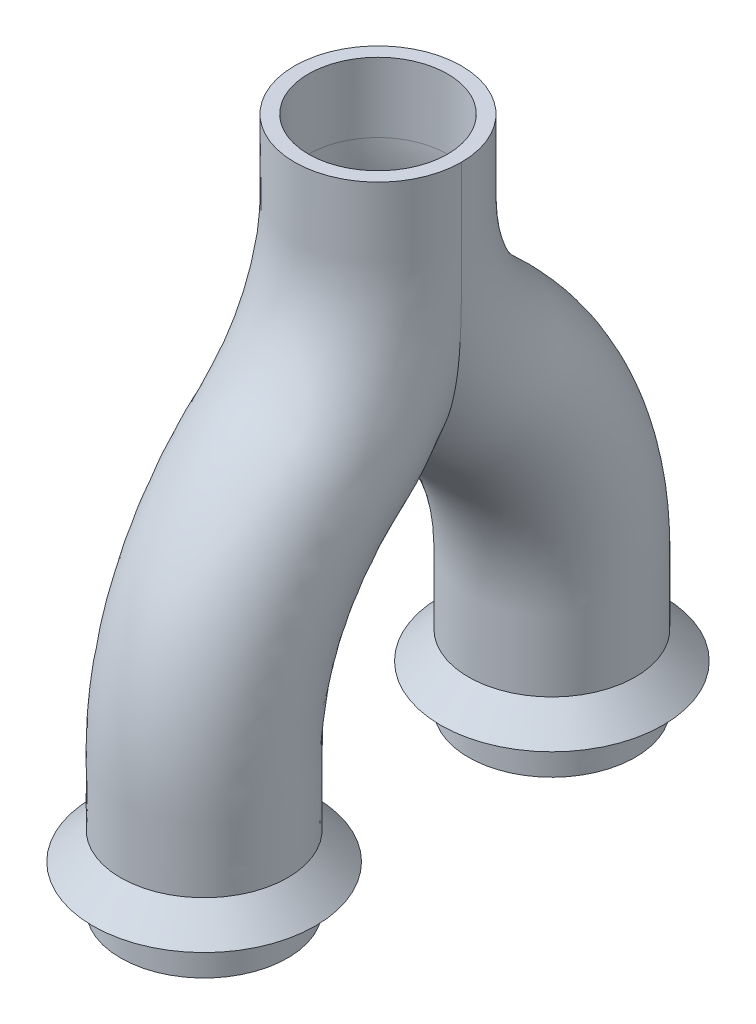
SolidWorks part; units mm, degrees
ref_plane "Front Plane" through (0, 0, 0) normal (0, 0, 1) x (1, 0, 0)
ref_plane "Top Plane" through (0, 0, 0) normal (0, 1, 0) x (1, 0, 0)
ref_plane "Right Plane" through (0, 0, 0) normal (1, 0, 0) x (0, 0, -1)
sketch "Sketch1" plane through (0, 0, 0) normal (1, 0, 0) x (0, 0, -1)
  line L0 (0, 39.1282) -> (0, -39.1282) construction
  line L1 (0, 5) -> (0, 0)
  line L2 (-12.5, -28.304) -> (12.5, -28.304) construction
  line L3 (-12.5, -28.304) -> (-12.5, -38.304)
  arc A0 (0, 0) -> (-5.8755, -13.304) centre (-18, 0) cw
  arc A1 (-5.8755, -13.304) -> (-12.5, -28.304) centre (7.7947, -28.304) ccw
  arc A2 (5.8755, -13.304) -> (12.5, -28.304) centre (-7.7947, -28.304) cw construction
  point P9 (0, -28.304)
  dimension "D1" = 18
  dimension "D5" = 5
  dimension "D3" = 25
  dimension "D4" = 15
  dimension "D6" = 10
sweep "Sweep1" add path "Sketch1" circular profile diameter 12 parameters "D3"=12
sketch "Sketch3" plane through (0, 0, 0) normal (1, 0, 0) x (0, 0, -1)
  line L0 (0, 39.1282) -> (0, -39.1282) construction
  line L1 (12.5, -28.304) -> (12.5, -38.304)
  line L2 (0, 0) -> (0, 5)
  arc A0 (5.8755, -13.304) -> (0, 0) centre (18, 0) cw
  arc A1 (5.8755, -13.304) -> (12.5, -28.304) centre (-7.7947, -28.304) cw
sweep "Sweep2" add path "Sketch3" circular profile diameter 12 parameters "D3"=12
sweep "Cut-Sweep1" cut path "Sketch1<5>" circular profile diameter 10 parameters "D3"=10
sketch "Sketch1<5>" plane through (0, 0, 0) normal (1, 0, 0) x (0, 0, -1) same geometry as "Sketch1"
sweep "Cut-Sweep2" cut path "Sketch3<2>" circular profile diameter 10 parameters "D3"=10
sketch "Sketch3<2>" plane through (0, 0, 0) normal (1, 0, 0) x (0, 0, -1) same geometry as "Sketch3"
sketch "Sketch111" plane through (0, 0, 0) normal (1, 0, 0) x (0, 0, -1)
  line L0 (0, 5.8563) -> (0, -38.6112) construction
  line L1 (6.5, -33.304) -> (4.5, -35.304)
  line L2 (4.5, -35.304) -> (6.5, -35.304)
  line L3 (6.5, -35.304) -> (6.5, -33.304)
  line L4 (-11.1452, 0) -> (10.6926, 0) construction
  line L8 (12.5, -38.304) -> (12.5, -25.4537) construction
  line L9 (6.5, -38.304) -> (18.5, -38.304) construction
  spline S0 degree 3 poles (0, -15.8745) (0.3018, -16.2167) (0.8618, -16.8163) (1.4517, -17.3864) (1.7573, -17.6685) (1.8046, -17.7119) (1.8671, -17.7688) (1.8797, -17.7804) (2.0617, -17.9485) (2.3957, -18.2713) (3.0528, -18.9713) (3.5183, -19.5519) (4.3865, -20.7582) (4.8813, -21.6228) (5.6818, -23.4354) (5.9875, -24.3835) (6.2944, -25.8377) (6.4099, -26.5728) (6.4823, -27.4992) (6.4964, -27.9325) (6.4996, -28.1801) (6.5, -28.2291) (6.5, -28.3928) (6.5, -28.5123) (6.5, -31.8457) (6.5, -35.0748) (6.5, -38.304) knots 0.397252 0.397252 0.397252 0.397252 0.418707 0.435817 0.435817 0.438261 0.438261 0.441017 0.441017 0.460309 0.482356 0.526451 0.526451 0.614641 0.614641 0.702831 0.702831 0.746926 0.768973 0.785509 0.785509 0.79102 0.79102 0.797551 0.797551 1 1 1 1 weights 1 1 1 1 1 1 1 1 1 1 1 1 1 1 1 1 1 1 1 1 1 1 1 1 1 1 1 construction
  dimension "D1" = 3
  dimension "D2" = 2
  dimension "D3" = 45
revolve "Revolve1" add sketch "Sketch111" angle 360 about L8
mirror "Mirror1" about plane through (0, 0, 0) normal (0, 0, 1) of "Revolve1"
